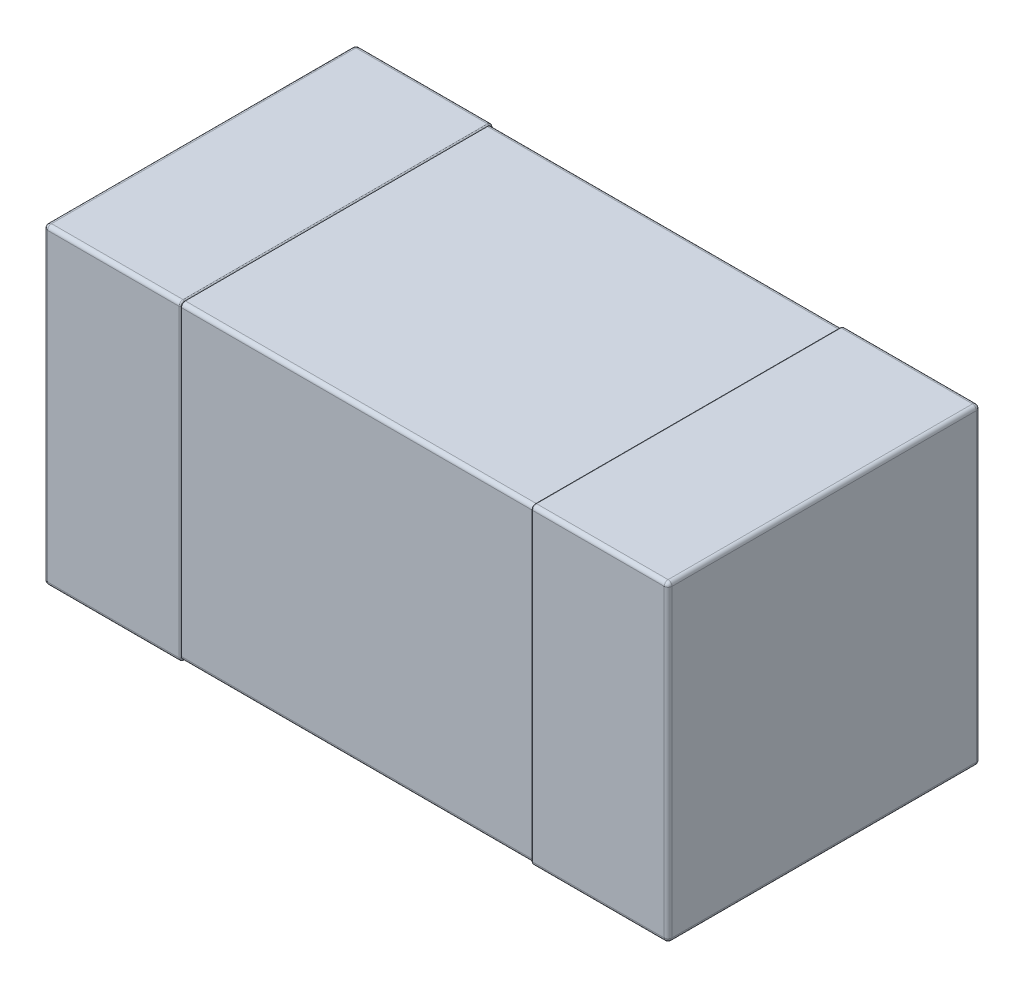
SolidWorks part; units mm, degrees
ref_plane "Top Plane" through (0, 0, 0) normal (0, 0, 1) x (1, 0, 0)
ref_plane "Front Plane" through (0, 0, 0) normal (0, 1, 0) x (1, 0, 0)
ref_plane "Side Plane" through (0, 0, 0) normal (1, 0, 0) x (0, 0, -1)
sketch "Sketch1" plane through (0, 0, 0) normal (0, 0, 1) x (1, 0, 0)
  line L1 (-0.8, 0.4) -> (0.8, 0.4)
  line L2 (-0.8, 0.4) -> (-0.8, -0.4)
  line L3 (-0.8, -0.4) -> (0.8, -0.4)
  line L4 (0.8, 0.4) -> (0.8, -0.4)
  dimension "D1" = 1.6
  dimension "D2" = 0.8
  dimension "D3" = 0.8
  dimension "D4" = 0.4
extrude "All body" add sketch "Sketch1" along normal blind 0.8
sketch "Sketch2" plane through (0, 0, 0) normal (1, 0, 0) x (0, 0, -1)
  line L14 (-0.003, 0.397) -> (-0.797, 0.397)
  line L15 (-0.003, -0.397) -> (-0.003, 0.397)
  line L16 (-0.797, -0.397) -> (-0.003, -0.397)
  line L17 (-0.797, 0.397) -> (-0.797, -0.397)
  line L18 (-0.003, 0.397) -> (-0.797, 0.397)
  line L19 (-0.003, -0.397) -> (-0.003, 0.397)
  line L20 (-0.797, -0.397) -> (-0.003, -0.397)
  line L21 (-0.797, 0.397) -> (-0.797, -0.397)
  dimension "D1" = 0.003
extrude "Cut out the body for pin" cut sketch "Sketch2" against normal blind 0.45 and the other way blind 0.45 flip side to cut
fillet "Body fillet" radius 0.01 4 edges at (0, 0.397, 0.003) (0, 0.397, 0.797) (0, -0.397, 0.003) (0, -0.397, 0.797)
fillet "Pin fillet a" radius 0.01 16 edges at (0.8, -0.4, 0.4) (0.8, 0, 0.8) (0.8, 0.4, 0.4) (0.8, 0, 0) (-0.8, 0.4, 0.4) (-0.8, 0, 0.8) (-0.8, -0.4, 0.4) (-0.8, 0, 0) (0.625, 0.4, 0.8) (0.625, -0.4, 0.8) (0.625, -0.4, 0) (0.625, 0.4, 0) (-0.625, 0.4, 0) (-0.625, -0.4, 0) (-0.625, 0.4, 0.8) (-0.625, -0.4, 0.8)
fillet "Pin fillet b" radius 0.003 16 edges at (0.45, -0.3971, 0.7971) (0.45, -0.4, 0.4) (0.45, -0.3971, 0.0029) (0.45, 0, 0) (0.45, 0.3971, 0.0029) (0.45, 0.4, 0.4) (0.45, 0.3971, 0.7971) (-0.45, -0.3971, 0.7971) (-0.45, -0.4, 0.4) (-0.45, -0.3971, 0.0029) (-0.45, 0, 0) (-0.45, 0.3971, 0.0029) (-0.45, 0.4, 0.4) (-0.45, 0.3971, 0.7971) (0.45, 0, 0.8) (-0.45, 0, 0.8)
